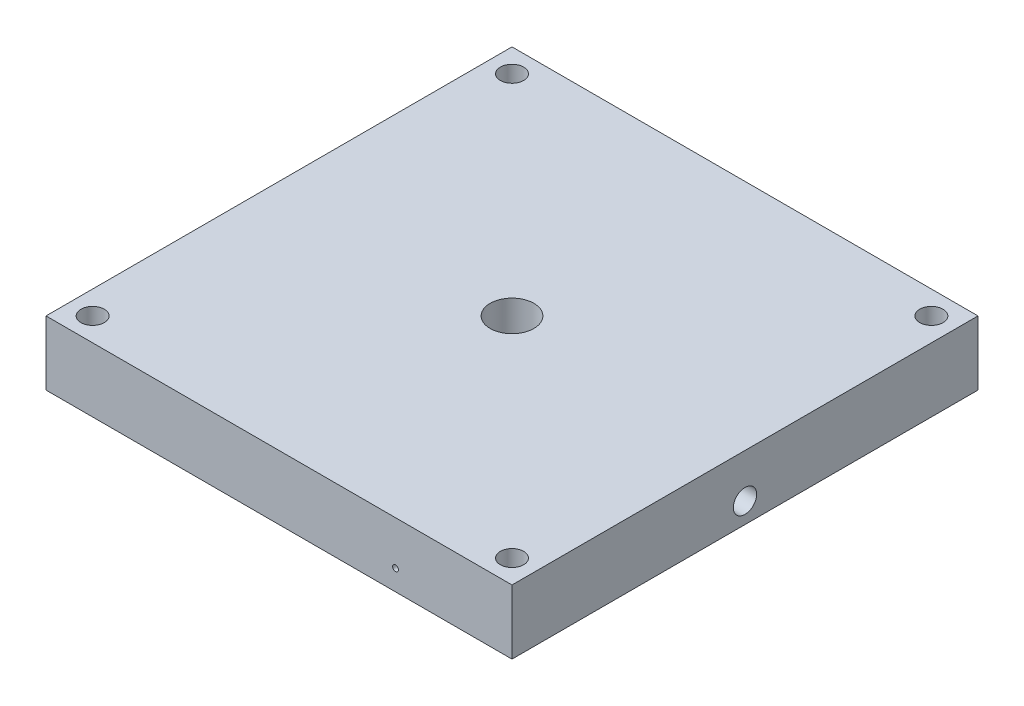
SolidWorks part; units mm, degrees
ref_plane "Front Plane" through (0, 0, 0) normal (0, 0, 1) x (1, 0, 0)
ref_plane "Top Plane" through (0, 0, 0) normal (0, 1, 0) x (1, 0, 0)
ref_plane "Right Plane" through (0, 0, 0) normal (1, 0, 0) x (0, 0, -1)
sketch "Sketch1" plane through (0, 0, 0) normal (0, 0, 1) x (1, 0, 0)
  line L0 (-38.1, 101.6046) -> (-38.1, 116.1639) construction
  line L1 (-32.1462, 17.5082) -> (0, 17.5082)
  line L2 (-32.1462, 17.5082) -> (-32.1462, 8.9687)
  line L3 (-27.1145, 0) -> (0, 0)
  line L4 (-32.1462, 8.9687) -> (-28.6385, 6.096)
  line L5 (0, 17.5082) -> (0, 0)
  line L12 (-27.1145, 3.4564) -> (-27.1145, 0)
  arc A0 (-27.1145, 3.4564) -> (-28.6385, 6.096) centre (-30.1625, 3.4564) ccw
  point P2 (0, 0)
  point P4 (0, 0)
  point P7 (0, 0)
  point P8 (-28.6385, 7.399)
  dimension "D9" = 3.048
  dimension "D1" = 5.9538
  dimension "D2" = 38.1
  dimension "D4" = 8.5395
  dimension "D7" = 10.9855
  dimension "D3" = 1.524
  dimension "D13" = 17.5082
  dimension "D8" = 8.9687
  dimension "D5" = 6.096
revolve "Revolve1" add sketch "Sketch1" angle 360 about L0
ref_axis "Axis1" through (-38.1, 17.5082, 0) along (0, -1, 0)
ref_plane "Plane2" through (38.1, 0, 0) normal (1, 0, 0) x (0, 0, -1)
sketch "Sketch5" plane through (0, 0, 0) normal (0, -1, 0) x (1, 0, 0)
  line L0 (-38.1, 0) -> (-101.6, 0) construction
  line L2 (-38.1, 0) -> (-38.1, 63.5) construction
  line L3 (-101.6, 0) -> (-101.6, 63.5) construction
  line L4 (-38.1, 63.5) -> (-101.6, 63.5) construction
  line L6 (-101.6, 63.5) -> (25.4, 63.5)
  line L7 (-101.6, 63.5) -> (-101.6, -63.5)
  line L8 (-101.6, -63.5) -> (25.4, -63.5)
  line L9 (25.4, 63.5) -> (25.4, -63.5)
  circle A0 centre (-38.1, 0) radius 38.1
  circle A1 centre (-95.25, 57.15) radius 3.175
  circle A2 centre (19.05, 57.15) radius 3.175
  circle A3 centre (19.05, -57.15) radius 3.175
  circle A4 centre (-95.25, -57.15) radius 3.175
  point P15 (0, 0)
  point P20 (-38.1, 0)
  point P22 (0, 0)
  dimension "D1" = 63.5
  dimension "D7" = 6.35
  dimension "D8" = 76.2
  dimension "D2" = 63.5
  dimension "D3" = 127
  dimension "D4" = 127
  dimension "D5" = 6.35
  dimension "D6" = 6.35
extrude "Boss-Extrude2" add sketch "Sketch5" against normal up to surface (17.5082 mm away) up to face at (-38.1, 17.5082, -5.9538)
sketch "Sketch4" plane through (0, 0, 0) normal (0, -1, 0) x (-1, 0, 0)
  line L0 (38.1, 0) -> (82.55, 0) construction
  circle A0 centre (82.55, 0) radius 1.0325
  circle A1 centre (38.1, 0) radius 44.45 construction
  dimension "D2" = 88.9
extrude "Cut-Extrude3" cut sketch "Sketch4" against normal blind 3.175
pattern_circular "CirPattern1" count 9 over 360 about axis through (-38.1, 17.5082, 0) along (0, -1, 0) of "Cut-Extrude3"
sketch "Sketch8" plane through (25.4, 0, 0) normal (1, 0, 0) x (0, 0, -1)
  line L0 (63.5, 0) -> (-63.5, 0) construction
  circle A0 centre (0, 5.588) radius 3.175
  dimension "EntranceDiameter" = 6.35
  dimension "D1" = 63.5
  dimension "D2" = 5.588
extrude "Cut-Extrude5" cut sketch "Sketch8" against normal up to surface (58.4635 mm away) up to face at (-38.1, 8.9687, -5.9538)
sketch "Sketch10" plane through (0, 0, 63.5) normal (0, 0, 1) x (1, 0, 0)
  line L0 (25.4, 0) -> (-101.6, 0) construction
  line L1 (-38.1, 17.5082) -> (-38.1, 8.9687) construction
  circle A0 centre (-6.35, 5.588) radius 0.7937
  point P2 (25.9192, -3.9183)
  point P3 (25.864, -1.9301)
  point P4 (23.4022, -3.6494)
  point P5 (23.3016, -1.9388)
  point P6 (23.4499, -3.9267)
  point P7 (23.6275, -1.8914)
  point P8 (23.8695, -3.9715)
  point P12 (-8.3514, 5.588)
  point P14 (-39.4911, -7.5084)
  dimension "D1" = 1.5875
  dimension "D2" = 5.588
  dimension "D3" = 31.75
extrude "Cut-Extrude9" cut sketch "Sketch10" against normal up to next
equation "\"ManifoldChamberThickness\" = 0.3031 + .05"
equation "\"AnnulusLength\"= 0.3362"
equation "\"D8@Sketch1\"=\"ManifoldChamberThickness\""
equation "\"D4@Sketch1\"=\"AnnulusLength\""
equation "\"AnnulusDiameter\"= 0.4688"
equation "\"D1@Sketch1\"=\"AnnulusDiameter\"/2"
equation "\"EntranceDiameter\"= .25"
equation "\"Basesidelength\"= 5"
equation "\"Basecenterdist\"= \"Basesidelength\" / 2"
equation "\"D1@Sketch8\"= \"Basecenterdist\""
equation "\"D4@Sketch5\"= \"Basesidelength\""
equation "\"D3@Sketch5\"= \"Basesidelength\""
equation "\"D1@Sketch5\"= \"Basecenterdist\""
equation "\"D2@Sketch5\"= \"Basecenterdist\""
